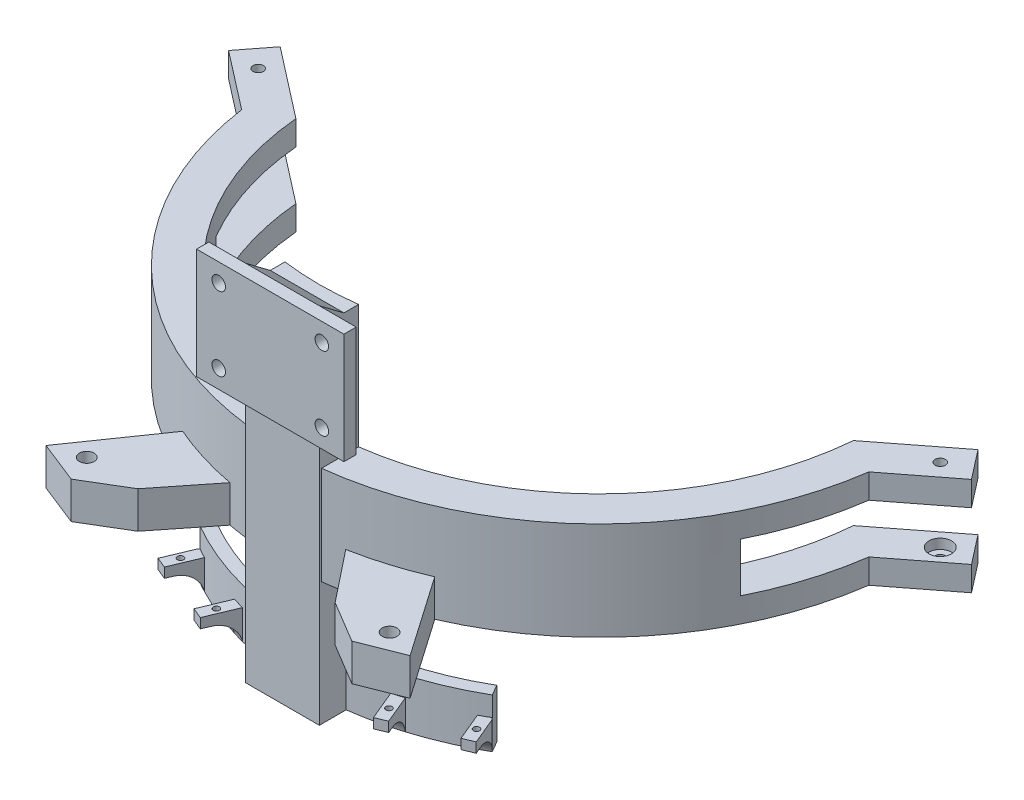
SolidWorks part; units mm, degrees
ref_plane "Front Plane" through (0, 0, 0) normal (0, 0, 1) x (1, 0, 0)
ref_plane "Top Plane" through (0, 0, 0) normal (0, 1, 0) x (1, 0, 0)
ref_plane "Right Plane" through (0, 0, 0) normal (1, 0, 0) x (0, 0, -1)
sketch "Sketch1" plane through (0, 0, 0) normal (0, 1, 0) x (1, 0, 0)
  line L0 (-192.7904, 0) -> (192.7904, 0) construction
  line L4 (127.7507, -17.91) -> (151.3112, 0.3239)
  line L6 (142.1225, 12.1647) -> (113.5606, -10)
  line L7 (0, 0) -> (-136.5479, 0) construction
  line L8 (-129, 0) -> (-114, 0)
  line L10 (125.6278, 0) -> (126.0239, -0.3282)
  line L11 (150.833, 0) -> (147.2463, -2.822)
  line L13 (0, 0) -> (0, -141.6679) construction
  line L14 (0, -55) -> (0, 55) construction
  line L15 (-150.833, 0) -> (-147.2463, -2.822)
  line L16 (-125.6278, 0) -> (-126.0239, -0.3282)
  line L17 (-142.1225, 12.1647) -> (-113.5606, -10)
  line L19 (-127.7507, -17.91) -> (-151.3111, 0.3239)
  line L20 (-151.3111, 0.3239) -> (-142.1225, 12.1647)
  line L21 (151.3112, 0.3239) -> (142.1225, 12.1647)
  arc A0 (-113.5606, -10) -> (113.5606, -10) centre (0, 0) ccw
  arc A1 (-127.7507, -17.91) -> (127.7507, -17.91) centre (0, 0) ccw
  circle A2 centre (138.9047, 0) radius 2.1
  circle A3 centre (-138.9047, 0) radius 2.1
  dimension "D1" = 228
  dimension "D2" = 258
  dimension "D4" = 4.2
  dimension "D3" = 10
  dimension "D5" = 10
  dimension "D7" = 10
extrude "Boss-Extrude1" add sketch "Sketch1" along normal mid plane 40
sketch "Sketch4" plane through (0, 0, 0) normal (1, 0, 0) x (0, 0, -1)
  line L0 (-57.8353, 10) -> (-57.8353, -10)
  line L1 (-57.8353, 10) -> (12.1647, 10)
  line L2 (-57.8353, -10) -> (12.1647, -10)
  line L3 (12.1647, 10) -> (12.1647, -10)
  line L4 (-17.91, 20) -> (-129, 20) construction
  line L5 (12.1647, 20) -> (12.1647, -20) construction
  dimension "D1" = 20
  dimension "D2" = 10
  dimension "D3" = 70
extrude "Cut-Extrude3" cut sketch "Sketch4" against normal mid plane 350
sketch "Sketch6" plane through (0, 0, 0) normal (0, 1, 0) x (1, 0, 0)
  line L0 (0, 0) -> (0, -156.0827) construction
  line L1 (-15, -113.0088) -> (-15, -129)
  line L2 (15, -113.0088) -> (15, -129)
  line L3 (-15, -129) -> (15, -129)
  arc A0 (-113.5606, -10) -> (113.5606, -10) centre (0, 0) ccw construction
  arc A1 (-15, -113.0088) -> (15, -113.0088) centre (0, 0) ccw
  arc A5 (-127.7507, -17.91) -> (127.7507, -17.91) centre (0, 0) ccw construction
  point P11 (0, -129)
  dimension "D1" = 30
extrude "Boss-Extrude2" add sketch "Sketch6" along normal mid plane 140.5
sketch "Sketch8" plane through (0, -70.25, 0) normal (0, -1, 0) x (1, 0, 0)
  line L0 (0, 114) -> (0, 119) construction
  line L1 (-57, 98.7269) -> (-59.5, 103.057) construction
  line L2 (57, 98.7269) -> (59.5, 103.057) construction
  line L3 (-59.5, 103.057) -> (-56.9689, 98.7448)
  line L4 (59.5, 103.057) -> (57, 98.7269)
  arc A0 (57, 98.7269) -> (-57, 98.7269) centre (0, 0) ccw
  arc A1 (59.5, 103.057) -> (-59.5, 103.057) centre (0, 0) ccw
  line M6 (-15, 129) -> (-15, 113.0088)
  arc M7 (-15, 113.0088) -> (15, 113.0088) centre (0, 0) cw
  line M8 (15, 113.0088) -> (15, 129)
  dimension "D1" = 5
  dimension "D2" = 30
  dimension "D3" = 30
extrude "Boss-Extrude4" add sketch "Sketch8" against normal blind 20 contours A1 M8 M6 M7 | A1 L3 A0 M6 | L4 A1 A0 M8
sketch "Sketch11" plane through (0, 0, 0) normal (0, 1, 0) x (1, 0, 0)
  circle A0 centre (-138.9047, 0) radius 4.6
  circle A1 centre (138.9047, 0) radius 4.6
  dimension "D1" = 9.2
  dimension "D2" = 9.2
extrude "Cut-Extrude5" cut sketch "Sketch11" against normal mid plane 28
sketch "Sketch12" plane through (0, 0, 0) normal (0, 1, 0) x (1, 0, 0)
  line L4 (-74.1551, -151.1981) -> (-51.337, -118.3449)
  line L5 (-74.1551, -151.1981) -> (-57.1751, -157.9236)
  line L6 (-57.1751, -157.9236) -> (-40.1897, -147.7596)
  line L7 (-40.1897, -147.7596) -> (-23.5706, -126.8283)
  arc A2 (-127.7507, -17.91) -> (-15, -128.1249) centre (0, 0) ccw construction
  arc A3 (-51.337, -118.3449) -> (-23.5706, -126.8283) centre (0, 0) ccw
  dimension "D1" = 40
extrude "Boss-Extrude6" add sketch "Sketch12" against normal blind 15 from offset 5 offset against normal yes
sketch "Sketch18" plane through (0, 0, 0) normal (0, 1, 0) x (1, 0, 0)
  circle A0 centre (-172.3523, -28.7654) radius 162 construction
  circle A1 centre (-61.6796, -147.0682) radius 3
  dimension "D1" = 6
extrude "Cut-Extrude7" cut sketch "Sketch18" against normal blind 30
mirror "Mirror2" about plane through (0, 0, 0) normal (1, 0, 0) of "Boss-Extrude6", "Cut-Extrude7"
sketch "Sketch19" plane through (0, 0, 129) normal (0, 0, 1) x (1, 0, 0)
  line L0 (-30, 77.75) -> (30, 77.75)
  line L1 (-30, 77.75) -> (-30, 32.75)
  line L2 (-30, 32.75) -> (30, 32.75)
  line L3 (30, 77.75) -> (30, 32.75)
  line L4 (-30, 77.75) -> (30, 32.75) construction
  line L5 (-30, 32.75) -> (30, 77.75) construction
  line L6 (-21, 70.25) -> (21, 70.25) construction
  line L7 (-21, 70.25) -> (-21, 40.25) construction
  line L8 (-21, 40.25) -> (21, 40.25) construction
  line L9 (21, 70.25) -> (21, 40.25) construction
  line L10 (-21, 70.25) -> (21, 40.25) construction
  line L11 (-21, 40.25) -> (21, 70.25) construction
  line L12 (-15, 70.25) -> (15, 70.25) construction
  circle A0 centre (-21, 70.25) radius 2.75
  circle A1 centre (21, 70.25) radius 2.75
  circle A2 centre (21, 40.25) radius 2.75
  circle A3 centre (-21, 40.25) radius 2.75
  point P0 (0, 55.25)
  point P5 (0, 55.25)
  dimension "D1" = 42
  dimension "D2" = 30
  dimension "D3" = 45
  dimension "D4" = 60
extrude "Boss-Extrude7" add sketch "Sketch19" along normal blind 5
sketch "Sketch20" plane through (0, 0, 0) normal (1, 0, 0) x (0, 0, -1)
  line L0 (-129, 77.75) -> (-119, 70.25)
  line L1 (-129, 77.75) -> (-129, 70.25)
  line L2 (-129, 32.75) -> (-129, 77.75) construction
  line L3 (-129, 70.25) -> (-119, 70.25)
  line L4 (-129, 70.25) -> (-113.0088, 70.25) construction
  dimension "D1" = 7.5
  dimension "D2" = 10
extrude "Boss-Extrude8" add sketch "Sketch20" along normal mid plane 30
sketch "Sketch21" plane through (0, -70.25, 0) normal (0, -1, 0) x (1, 0, 0)
  line L0 (30.6444, 116.1707) -> (45.4054, 109.997) construction
  line L1 (60.1663, 103.8234) -> (64.7966, 114.8941)
  line L2 (64.7966, 114.8941) -> (60.4144, 116.7269)
  line L3 (60.4144, 116.7269) -> (55.7842, 105.6562)
  line L4 (30.6444, 116.1707) -> (35.2747, 127.2414)
  line L5 (-15, 129) -> (-15, 118.0508)
  line L6 (-59.5, 103.057) -> (-56.9689, 98.7448)
  line L7 (57, 98.7269) -> (59.5, 103.057)
  line L8 (15, 118.0508) -> (15, 129)
  line L9 (15, 129) -> (-15, 129)
  line L15 (35.2747, 127.2414) -> (39.6568, 125.4086)
  line L16 (39.6568, 125.4086) -> (35.0266, 114.3379)
  line L17 (35.1506, 120.7897) -> (60.2904, 110.2752) construction
  line L18 (37.4658, 126.325) -> (32.8355, 115.2543) construction
  line L19 (62.6055, 115.8105) -> (57.9753, 104.7398) construction
  line L20 (60.1663, 103.8234) -> (59.5, 103.057)
  line L21 (55.7842, 105.6562) -> (55.5988, 105.213)
  line L22 (30.6444, 116.1707) -> (30.1985, 115.1045)
  line L23 (35.0266, 114.3379) -> (34.8007, 113.7977)
  line L24 (46.4268, 109.5698) -> (60.1663, 103.8234) construction
  arc A0 (59.5, 103.057) -> (15, 118.0508) centre (0, 0) ccw construction
  circle A1 centre (35.1506, 120.7897) radius 1.25
  circle A2 centre (60.2904, 110.2752) radius 1.25
  arc A3 (-15, 118.0508) -> (-59.5, 103.057) centre (0, 0) ccw
  arc A4 (57, 98.7269) -> (-56.9689, 98.7448) centre (0, 0) ccw
  arc A5 (59.5, 103.057) -> (15, 118.0508) centre (0, 0) ccw
  arc A8 (59.5, 103.057) -> (55.5988, 105.213) centre (0, 0) ccw
  arc A9 (34.8007, 113.7977) -> (30.1985, 115.1045) centre (0, 0) ccw
  point P15 (45.4054, 109.997)
  dimension "D11" = 2.5
  dimension "D12" = 2.5
  dimension "D2" = 6
  dimension "D3" = 32
  dimension "D4" = 4.75
  dimension "D5" = 22.5
  dimension "D6" = 4.75
  dimension "D7" = 12
  dimension "D8" = 12
  dimension "D9" = 12
  dimension "D10" = 12
  dimension "D1" = 0
extrude "Boss-Extrude9" add sketch "Sketch21" along normal blind 4 from offset 12 offset against normal yes
fillet "Fillet1" radius 10 2 edges at (57.5595, -62.25, 104.1533) (32.5061, -62.25, 114.4742)
mirror "Mirror3" about plane through (0, 0, 0) normal (1, 0, 0) of "Fillet1", "Boss-Extrude9"
